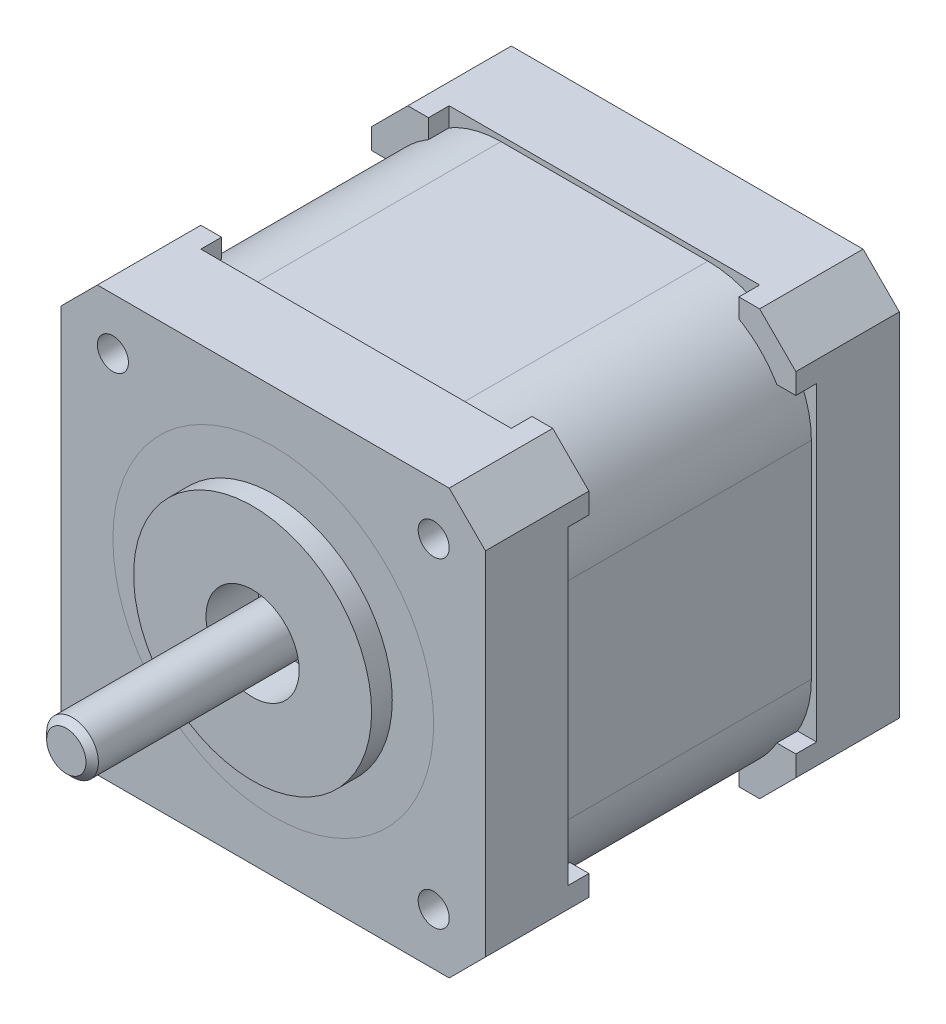
SolidWorks part; units mm, degrees
ref_plane "Alzado" through (0, 0, 0) normal (0, 0, 1) x (1, 0, 0)
ref_plane "Planta" through (0, 0, 0) normal (0, 1, 0) x (1, 0, 0)
ref_plane "Vista lateral" through (0, 0, 0) normal (1, 0, 0) x (0, 0, -1)
sketch "Croquis1" plane through (0, 0, 0) normal (0, 0, 1) x (1, 0, 0)
  line L2 (0, 15) -> (-15, 15) construction
  line L3 (-15, -15) -> (-15, 15) construction
  line L4 (-17, 20.5) -> (-20.5, 17)
  line L5 (15, -15) -> (15, 15) construction
  line L6 (0, 20.5) -> (0, -20.5) construction
  line L7 (-20.5, 0) -> (20.5, 0) construction
  line L8 (20.5, 17) -> (20.5, -17)
  line L9 (17, 20.5) -> (20.5, 17)
  line L10 (0, -15) -> (-15, -15) construction
  line L11 (17, -20.5) -> (-17, -20.5)
  line L12 (17, -20.5) -> (20.5, -17)
  line L13 (-17, -20.5) -> (-20.5, -17)
  line L16 (17, 20.5) -> (-17, 20.5)
  line L18 (-20.5, 17) -> (-20.5, -17)
  circle A0 centre (-15, 15) radius 3
  circle A1 centre (15, 15) radius 3
  circle A2 centre (15, -15) radius 3
  circle A3 centre (-15, -15) radius 3
  point P1 (-20.5, 20.5)
  point P23 (20.5, 20.5)
  point P25 (0, 0)
  point P26 (15, 0)
  point P27 (-15, 0)
  point P34 (20.5, -20.5)
  point P35 (-20.5, -20.5)
  dimension "D4" = 6
  dimension "D2" = 30
  dimension "D3" = 15
  dimension "D1" = 41
extrude "Saliente-Extruir1" add sketch "Croquis1" along normal mid plane 40 contours L16 L4 L18 L13 L11 L12 L8 L9
sketch "Croquis2" plane through (0, 0, 20) normal (0, 0, 1) x (1, 0, 0)
  line L0 (20.5, -15) -> (-20.5, -15)
  line L1 (20.5, -15) -> (20.5, 15)
  line L2 (-20.5, -15) -> (-20.5, 15)
  line L3 (20.5, 15) -> (-20.5, 15)
  line L4 (20.5, -15) -> (-20.5, 15) construction
  line L5 (-20.5, -15) -> (20.5, 15) construction
  line L6 (-20.5, 17) -> (-20.5, -17) construction
  line L7 (17, 20.5) -> (-17, 20.5) construction
  line L8 (15, -20.5) -> (-15, -20.5)
  line L9 (15, -20.5) -> (15, 20.5)
  line L10 (15, 20.5) -> (-15, 20.5)
  line L11 (-15, -20.5) -> (-15, 20.5)
  line L12 (15, -20.5) -> (-15, 20.5) construction
  line L13 (15, 20.5) -> (-15, -20.5) construction
  point P1 (0, 0)
  point P3 (0, 0)
  line M10 (17, 20.5) -> (-17, 20.5)
  line M12 (-20.5, 17) -> (-20.5, -17)
  line M14 (-17, -20.5) -> (17, -20.5)
  line M16 (20.5, -17) -> (20.5, 17)
  dimension "D1" = 30
extrude "Cortar-Extruir1" cut sketch "Croquis2" against normal offset from surface (24 mm away) 8 from offset 8 contours L11 L3 L9 M10 | L11 L0 L9 L3 | L9 L0 L3 M16 | L11 L9 L0 M14 | L0 L11 L3 M12 region at (17.75, 0, 20) region at (0, -17.75, 20) region at (0, 0, 20) region at (-17.75, 0, 20) region at (0, 17.75, 20) up to face at (0, 0, -20) offset against normal yes
sketch "Croquis3" plane through (0, 0, -20) normal (0, 0, -1) x (-1, 0, 0)
  line L8 (-17, 20.5) -> (-20.5, 17)
  line L9 (-20.5, 17) -> (-20.5, -17)
  line L10 (-20.5, -17) -> (-17, -20.5)
  line L11 (-17, -20.5) -> (17, -20.5)
  line L12 (17, -20.5) -> (20.5, -17)
  line L13 (20.5, -17) -> (20.5, 17)
  line L14 (20.5, 17) -> (17, 20.5)
  line L15 (17, 20.5) -> (-17, 20.5)
  line L16 (-17, 20.5) -> (-20.5, 17)
  line L17 (-20.5, 17) -> (-20.5, -17)
  line L18 (-20.5, -17) -> (-17, -20.5)
  line L19 (-17, -20.5) -> (17, -20.5)
  line L20 (17, -20.5) -> (20.5, -17)
  line L21 (20.5, -17) -> (20.5, 17)
  line L22 (20.5, 17) -> (17, 20.5)
  line L23 (17, 20.5) -> (-17, 20.5)
  dimension "D1" = 0
extrude "Cortar-Extruir2" cut sketch "Croquis3" against normal offset from surface (20 mm away) 10 from offset 10 up to face at (0, 0, 20) offset against normal yes
sketch "Croquis4" plane through (0, 0, 20) normal (0, 0, 1) x (1, 0, 0)
  line L2 (-20, 10) -> (-20, -10)
  line L3 (10, 20) -> (-10, 20)
  line L4 (17, 20.5) -> (-17, 20.5) construction
  line L5 (-20.5, 17) -> (-20.5, -17) construction
  line L6 (0, -1000) -> (0, 49000) construction
  line L7 (-1000, 0) -> (49000, 0) construction
  line L8 (20, 10) -> (20, -10)
  line L9 (10, -20) -> (-10, -20)
  arc A4 (-10, 20) -> (-20, 10) centre (-10, 10) ccw
  arc A5 (10, 20) -> (20, 10) centre (10, 10) cw
  arc A6 (10, -20) -> (20, -10) centre (10, -10) ccw
  arc A7 (-10, -20) -> (-20, -10) centre (-10, -10) cw
  dimension "D1" = 10
  dimension "D3" = 0.5
  dimension "D4" = 0.5
extrude "Cortar-Extruir3" cut sketch "Croquis4<4>" against normal up to surface (32 mm away) from surface up to face at (0, 0, -12) starting at face at (0, 0, 12)
sketch "Croquis4<4>" plane through (0, 0, 20) normal (0, 0, 1) x (1, 0, 0) same geometry as "Croquis4"
extrude "Saliente-Extruir2" add sketch "Croquis4" against normal up to next from surface separate body contours A5 L8 A6 L9 A7 L2 A4 L3 starting at face at (0, 0, 12)
sketch "Croquis5" plane through (0, 0, 20) normal (0, 0, 1) x (1, 0, 0)
  circle A0 centre (0, 0) radius 15.5
  circle A1 centre (0, 0) radius 11.5
  circle A2 centre (0, 0) radius 4.5
  circle A3 centre (0, 0) radius 2.5
  dimension "D1" = 31
  dimension "D2" = 23
  dimension "D3" = 9
  dimension "D4" = 5
extrude "Cortar-Extruir4" cut sketch "Croquis5" against normal blind 3 contours A0 A1 | A1 A2 | A2 A3 | A3 region at (-15.0616, 0, 20) region at (-11.1747, 0, 20) region at (-4.3727, 0, 20) region at (0, 0, 20)
extrude "Saliente-Extruir3" add sketch "Croquis5<3>" against normal up to body separate body contours A0 A1 region at (-15.0616, 0, 20)
sketch "Croquis5<3>" plane through (0, 0, 20) normal (0, 0, 1) x (1, 0, 0) same geometry as "Croquis5"
extrude "Saliente-Extruir4" add sketch "Croquis5<4>" along normal blind 5 from surface separate body contours A1 A2 region at (-11.1747, 0, 20) starting at face at (15.5, 0, 17)
sketch "Croquis5<4>" plane through (0, 0, 20) normal (0, 0, 1) x (1, 0, 0) same geometry as "Croquis5"
extrude "Saliente-Extruir5" add sketch "Croquis5<5>" along normal blind 23 from surface contours A3 region at (0, 0, 20) starting at face at (15.5, 0, 17)
sketch "Croquis5<5>" plane through (0, 0, 20) normal (0, 0, 1) x (1, 0, 0) same geometry as "Croquis5"
chamfer "Chaflán1" distance 0.6 angle 45 1 edges at (2.5, 0, 40)
sketch "Croquis6" plane through (0, 0, 20) normal (0, 0, 1) x (1, 0, 0)
  line L0 (15.5, -15.5) -> (15.5, 15.5) construction
  line L1 (15.5, -15.5) -> (-15.5, -15.5) construction
  line L2 (15.5, 15.5) -> (-15.5, 15.5) construction
  line L3 (-15.5, -15.5) -> (-15.5, 15.5) construction
  line L4 (15.5, -15.5) -> (-15.5, 15.5) construction
  line L5 (15.5, 15.5) -> (-15.5, -15.5) construction
  circle A0 centre (-15.5, 15.5) radius 1.5
  circle A1 centre (15.5, -15.5) radius 1.5
  circle A2 centre (15.5, 15.5) radius 1.5
  circle A3 centre (-15.5, -15.5) radius 1.5
  point P3 (0, 0)
  dimension "D2" = 3
  dimension "D1" = 31
extrude "Cortar-Extruir5" cut sketch "Croquis6" against normal blind 6 contours A3 | A1 | A2 | A0 region at (15.5, -15.5, 20) region at (15.5, 15.5, 20) region at (-15.5, -15.5, 20)
